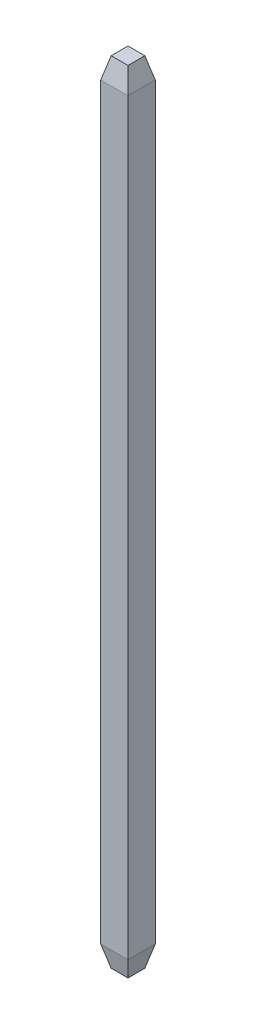
SolidWorks part; units mm, degrees
other "Camera1"
material "1060 Alloy"
ref_plane "Front Plane" through (0, 0, 0) normal (0, 0, 1) x (1, 0, 0)
ref_plane "Top Plane" through (0, 0, 0) normal (0, 1, 0) x (1, 0, 0)
ref_plane "Right Plane" through (0, 0, 0) normal (1, 0, 0) x (0, 0, -1)
sketch "Sketch1" plane through (0, 0, 0) normal (0, 1, 0) x (1, 0, 0)
  line L1 (-0.325, -0.325) -> (0.325, -0.325)
  line L2 (-0.325, -0.325) -> (-0.325, 0.325)
  line L3 (-0.325, 0.325) -> (0.325, 0.325)
  line L4 (0.325, -0.325) -> (0.325, 0.325)
  line L5 (-0.325, -0.325) -> (0.325, 0.325) construction
  line L6 (-0.325, 0.325) -> (0.325, -0.325) construction
  point P0 (0, 0)
  dimension "D1" = 0.65
extrude "Boss-Extrude1" add sketch "Sketch1" along normal mid plane 18.8
sketch "Sketch2" plane through (0, 9.4, 0) normal (0, 1, 0) x (1, 0, 0)
  line L1 (-0.2, -0.2) -> (0.2, -0.2)
  line L2 (-0.2, -0.2) -> (-0.2, 0.2)
  line L3 (-0.2, 0.2) -> (0.2, 0.2)
  line L4 (0.2, -0.2) -> (0.2, 0.2)
  line L5 (-0.2, -0.2) -> (0.2, 0.2) construction
  line L6 (-0.2, 0.2) -> (0.2, -0.2) construction
  point P0 (0, 0)
  dimension "D1" = 0.4
ref_plane "Plane1" through (0, 8.9, 0) normal (0, 1, 0) x (1, 0, 0)
sketch "Sketch3" plane through (0, 8.9, 0) normal (0, 1, 0) x (1, 0, 0)
  line L1 (0.325, -0.325) -> (-0.325, -0.325)
  line L2 (0.325, -0.325) -> (0.325, 0.325)
  line L3 (0.325, 0.325) -> (-0.325, 0.325)
  line L4 (-0.325, -0.325) -> (-0.325, 0.325)
  line L5 (0.325, -0.325) -> (-0.325, 0.325) construction
  line L6 (0.325, 0.325) -> (-0.325, -0.325) construction
  point P0 (0, 0)
extrude "Cut-Extrude1" cut sketch "Sketch3" along normal up to next
loft "Loft1" add profiles "Sketch3<3>", "Sketch2" connector at (-0.325, 8.9, -0.325) connector at (-0.2, 9.4, -0.2)
sketch "Sketch3<3>" plane through (0, 8.9, 0) normal (0, 1, 0) x (1, 0, 0) same geometry as "Sketch3"
mirror "Mirror1" about plane through (0, 0, 0) normal (0, 1, 0) of "Cut-Extrude1", "Loft1"
